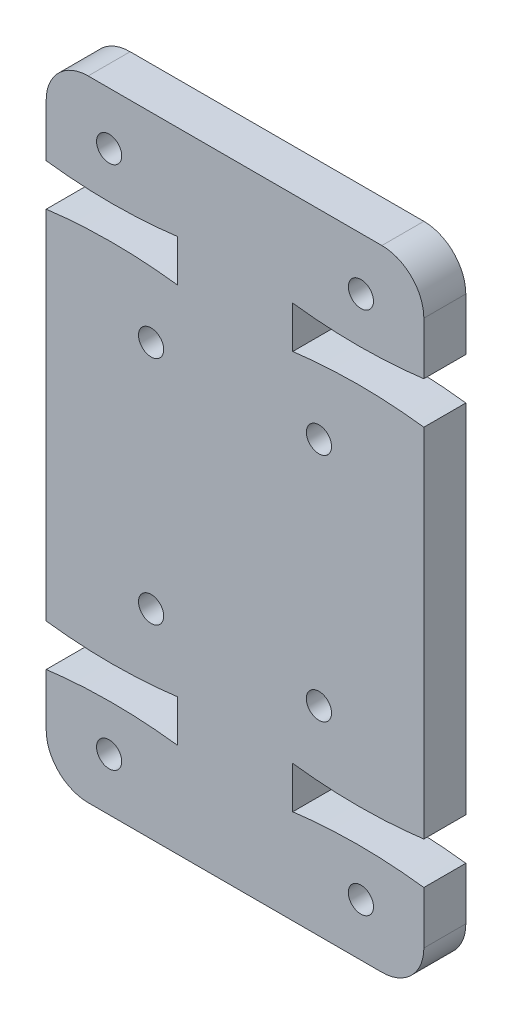
SolidWorks part; units mm, degrees
ref_plane "Front Plane" through (0, 0, 0) normal (0, 0, 1) x (1, 0, 0)
ref_plane "Top Plane" through (0, 0, 0) normal (0, 1, 0) x (1, 0, 0)
ref_plane "Right Plane" through (0, 0, 0) normal (1, 0, 0) x (0, 0, -1)
sketch "Sketch1" plane through (0, 0, 0) normal (0, 0, 1) x (1, 0, 0)
  line L0 (0, 6.5) -> (0, 23.5)
  line L1 (0, 0) -> (18, 0)
  line L2 (0, 25.5) -> (0, 30)
  line L3 (9, 30) -> (9, 0) construction
  line L4 (0, 15) -> (18, 15) construction
  line L5 (0, 4.5) -> (6.25, 4.5) construction
  line L6 (6.25, 4.5) -> (6.25, 6.5)
  line L7 (6.25, 6.5) -> (0, 6.5) construction
  line L8 (0, 4.5) -> (0, 0)
  line L9 (6.25, 23.5) -> (0, 23.5) construction
  line L10 (6.25, 25.5) -> (6.25, 23.5)
  line L11 (0, 25.5) -> (6.25, 25.5) construction
  line L12 (0, 30) -> (18, 30)
  line L13 (18, 25.5) -> (11.75, 25.5) construction
  line L14 (11.75, 25.5) -> (11.75, 23.5)
  line L15 (11.75, 23.5) -> (18, 23.5) construction
  line L16 (18, 4.5) -> (18, 0)
  line L17 (11.75, 6.5) -> (18, 6.5) construction
  line L18 (11.75, 4.5) -> (11.75, 6.5)
  line L19 (18, 4.5) -> (11.75, 4.5) construction
  line L20 (18, 25.5) -> (18, 30)
  line L21 (18, 6.5) -> (18, 23.5)
  line L22 (3.125, 4.5) -> (3.125, 4.7) construction
  line L23 (6.25, 5.5) -> (0, 5.5) construction
  circle A0 centre (3, 2.5) radius 0.6
  circle A1 centre (5, 9.5) radius 0.6
  circle A2 centre (5, 20.5) radius 0.6
  circle A3 centre (3, 27.5) radius 0.6
  circle A4 centre (15, 27.5) radius 0.6
  circle A5 centre (13, 20.5) radius 0.6
  circle A6 centre (13, 9.5) radius 0.6
  circle A7 centre (15, 2.5) radius 0.6
  spline S0 degree 2 poles (0, 4.5) (3.125, 4.9) (6.25, 4.5) knots 0 0 0 1 1 1
  spline S1 degree 2 poles (0, 6.5) (3.125, 6.1) (6.25, 6.5) knots 0 0 0 1 1 1
  spline S2 degree 2 poles (18, 4.5) (14.875, 4.9) (11.75, 4.5) knots 0 0 0 1 1 1
  spline S3 degree 2 poles (18, 6.5) (14.875, 6.1) (11.75, 6.5) knots 0 0 0 1 1 1
  spline S4 degree 2 poles (18, 25.5) (14.875, 25.1) (11.75, 25.5) knots 0 0 0 1 1 1
  spline S5 degree 2 poles (18, 23.5) (14.875, 23.9) (11.75, 23.5) knots 0 0 0 1 1 1
  spline S6 degree 2 poles (0, 25.5) (3.125, 25.1) (6.25, 25.5) knots 0 0 0 1 1 1
  spline S7 degree 2 poles (0, 23.5) (3.125, 23.9) (6.25, 23.5) knots 0 0 0 1 1 1
  point P23 (9, 15)
  dimension "D1" = 1.2
  dimension "D2" = 3
  dimension "D3" = 2.5
  dimension "D4" = 4.5
  dimension "D5" = 2
  dimension "D6" = 6.25
  dimension "D7" = 5
  dimension "D8" = 9.5
  dimension "D9" = 9
  dimension "D10" = 15
  dimension "D11" = 0.2
extrude "Finger PIP Body" add sketch "Sketch1" along normal blind 2
fillet "Finger PIP Contouring" radius 2 4 edges at (0, 30, 1) (18, 30, 1) (18, 0, 1) (0, 0, 1)
equation "\"D10@Sketch1\"=\"Lp@Parameters@RobotHandParameters.SLDPRT\"/2"
equation "\"D9@Sketch1\"=\"Wph@Parameters@RobotHandParameters.SLDPRT\"/2"
equation "\"D11@Sketch1\"=\"radii_fit@Parameters@RobotHandParameters.SLDPRT\""
equation "\"D1@Sketch1\"=1+\"cut_free@Parameters@RobotHandParameters.SLDPRT\""
